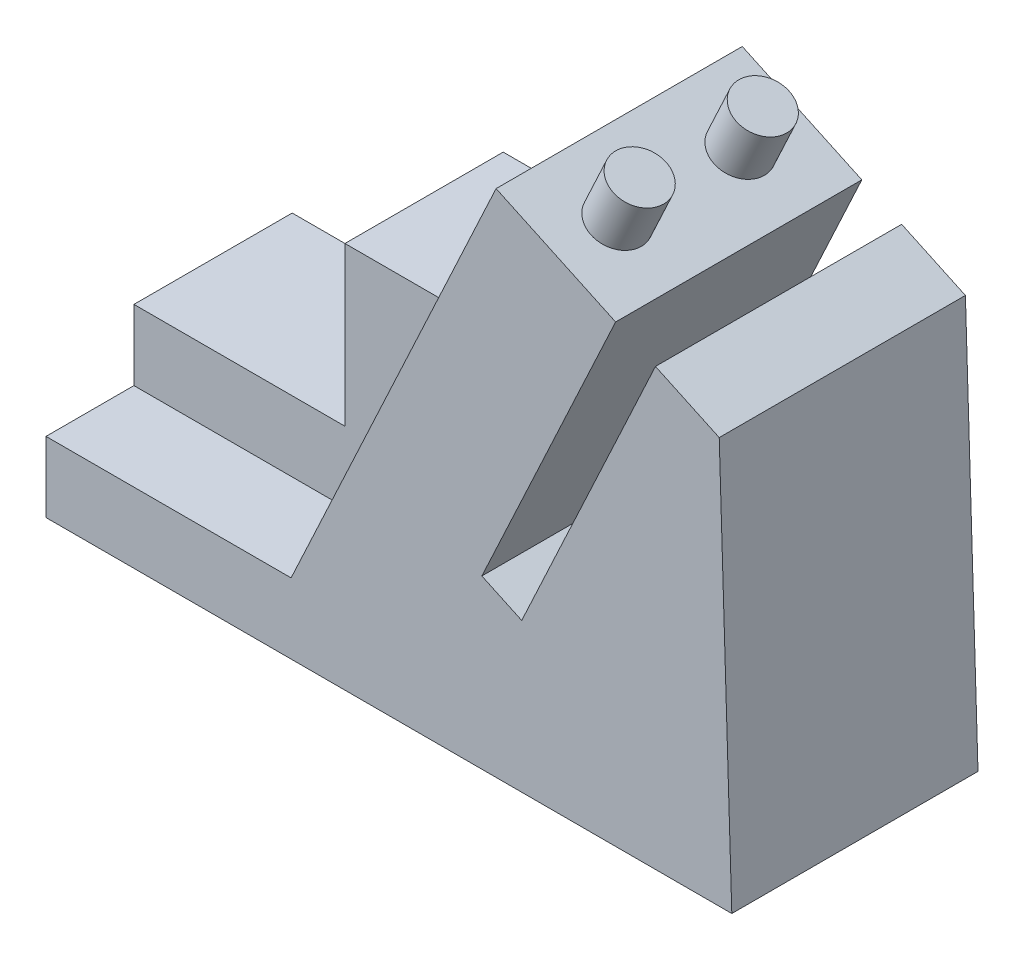
SolidWorks part; units mm, degrees
ref_plane "Front Plane" through (0, 0, 0) normal (0, 0, 1) x (1, 0, 0)
ref_plane "Top Plane" through (0, 0, 0) normal (0, 1, 0) x (1, 0, 0)
ref_plane "Right Plane" through (0, 0, 0) normal (1, 0, 0) x (0, 0, -1)
sketch "Sketch1" plane through (0, 0, 0) normal (0, 0, 1) x (1, 0, 0)
  line L0 (0, 0) -> (78, 0)
  line L3 (69.3175, 49.5476) -> (54.1033, 16.9206)
  line L4 (54.1033, 16.9206) -> (49.5717, 19.0336)
  line L5 (49.5717, 19.0336) -> (64.786, 51.6607)
  line L6 (64.786, 51.6607) -> (51.1914, 58)
  line L7 (51.1914, 58) -> (27.876, 8)
  line L8 (27.876, 8) -> (0, 8)
  line L9 (0, 8) -> (0, 0)
  line L10 (0, 8) -> (0, 16)
  line L11 (0, 16) -> (24, 16)
  line L12 (24, 16) -> (24, 34)
  line L13 (24, 34) -> (40, 34)
  line L14 (78, 0) -> (76.568, 46.1667)
  line L15 (76.568, 46.1667) -> (69.3175, 49.5476)
  point P3 (76.6338, 53.8537)
  point P4 (76.1225, 46.3745)
  point P17 (78, 45.513)
  dimension "D1" = 78
  dimension "D2" = 8
  dimension "D3" = 24
  dimension "D4" = 65
  dimension "D5" = 16
  dimension "D6" = 5
  dimension "D7" = 36
  dimension "D8" = 15
  dimension "D9" = 16
  dimension "D10" = 18
  dimension "D11" = 58
  dimension "D12" = 8
extrude "Boss-Extrude1" add sketch "Sketch1" along normal blind 28 contours L9 L0 L14 L15 L3 L4 L5 L6 L7 L8
extrude "Boss-Extrude2" add sketch "Sketch1<3>" along normal blind 18 contours L13 L12 L11 L10 L8 L7 region at (0.4771, 12, 0)
sketch "Sketch1<3>" plane through (0, 0, 0) normal (0, 0, 1) x (1, 0, 0) same geometry as "Sketch1"
sketch "Sketch2" plane through (31.3584, 67.2483, 0) normal (0.4226, 0.9063, 0) x (0.9063, -0.4226, 0)
  line L0 (21.8833, -28) -> (21.8833, 0) construction
  line L1 (36.8833, 0) -> (21.8833, 0) construction
  line L2 (36.8833, -28) -> (21.8833, -28) construction
  circle A0 centre (29.3833, -7) radius 3
  circle A1 centre (29.3833, -21) radius 3
  dimension "D1" = 6
  dimension "D4" = 6
  dimension "D2" = 7.5
  dimension "D3" = 7
  dimension "D5" = 7
  dimension "D6" = 7.5
extrude "Boss-Extrude3" add sketch "Sketch2" along normal blind 6
